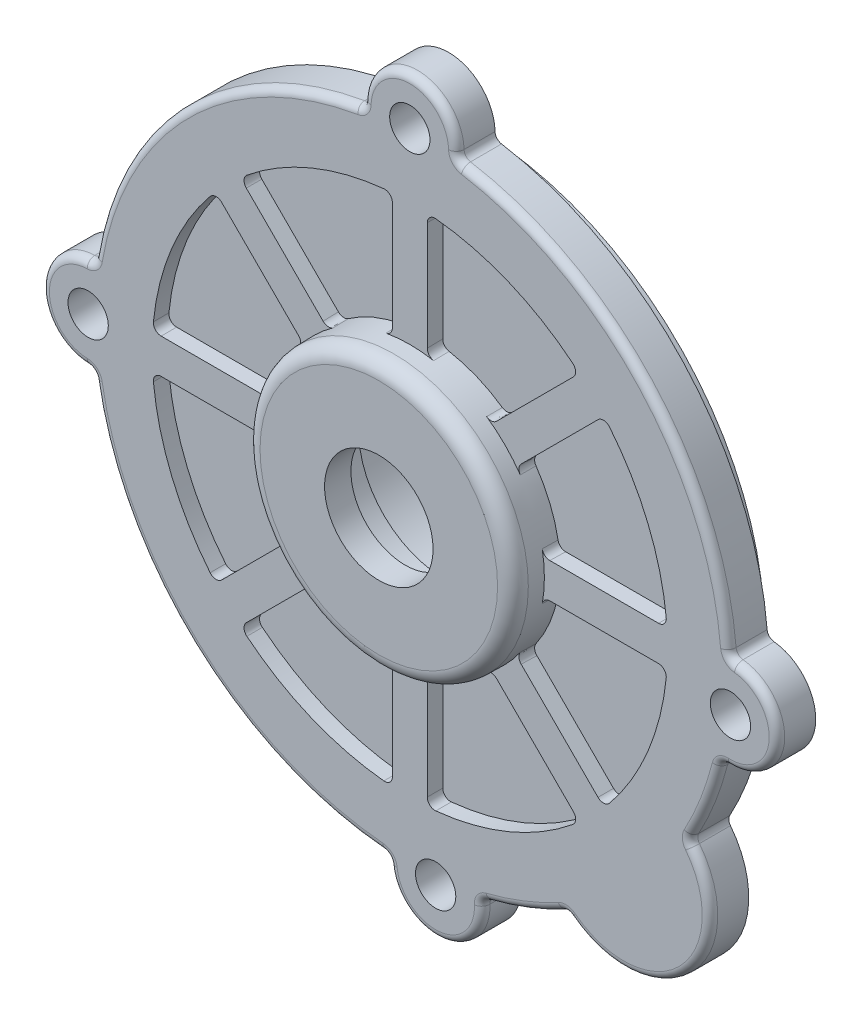
SolidWorks part; units mm, degrees
material "356.0-T6 Moulage permanent (SS)"
ref_plane "Plan de face" through (0, 0, 0) normal (0, 0, 1) x (1, 0, 0)
ref_plane "Plan de dessus" through (0, 0, 0) normal (0, 1, 0) x (1, 0, 0)
ref_plane "Plan de droite" through (0, 0, 0) normal (1, 0, 0) x (0, 0, -1)
ref_axis "Axe1" through (0, 0, 0) along (0, 0, 1)
sketch "Esquisse17" plane through (0, 0, 0) normal (0, 0, 1) x (1, 0, 0)
  line L0 (0, 0) -> (-27.5772, 27.5772) construction
  line L1 (65.7399, 0) -> (-65.7399, 0) construction
  line L2 (-27.5772, 69.0772) -> (-27.5772, 27.5772) construction
  line L3 (-69.0772, 27.5772) -> (-27.5772, 27.5772) construction
  line L4 (-30.7591, 30.7591) -> (30.7591, 30.7591) construction
  line L5 (30.7591, 30.7591) -> (30.7591, -30.7591) construction
  line L6 (-30.7591, 30.7591) -> (-30.7591, -30.7591) construction
  line L7 (30.7591, -30.7591) -> (-30.7591, -30.7591) construction
  line L8 (0, 0) -> (30.7591, 30.7591) construction
  circle A0 centre (0, 0) radius 50.45
  circle A1 centre (-27.5772, 27.5772) radius 41.25
  circle A2 centre (-27.5772, 27.5772) radius 41.5 construction
  circle A3 centre (0, 0) radius 43.5 construction
  point P8 (13.7889, 24.2458)
  point P9 (-24.2458, -13.7889)
  point P10 (-27.5772, 69.0772)
  point P11 (-69.0772, 27.5772)
  dimension "D1" = 100.9
  dimension "D2" = 82.5
  dimension "D8" = 58.6899
  dimension "D6" = 83
  dimension "D9" = 87
  dimension "D3" = 39
  dimension "D4" = 45
  dimension "D5" = 61
  dimension "D7" = 53.7893
ref_axis "Axe2" through (-27.5772, 27.5772, 0) along (0, 0, 1)
ref_plane "Plan1" through (-27.5772, 0, 0) normal (1, 0, 0) x (0, 0, -1)
sketch "Esquisse18" plane through (0, 0, 0) normal (0, 0, 1) x (1, 0, 0)
  arc A0 (2.9197, 7.0709) -> (-7.0709, -2.9197) centre (-27.5772, 27.5772) ccw
  arc A1 (8.3776, 7.3579) -> (-7.3579, -8.3776) centre (-27.5772, 27.5772) ccw
  arc A2 (-7.3579, -8.3776) -> (8.3776, 7.3579) centre (0, 0) ccw
  arc A3 (-7.0709, -2.9197) -> (2.9197, 7.0709) centre (0, 0) ccw
  dimension "D1" = 4.5
  dimension "D2" = 82.5
  dimension "D3" = 91.4
  dimension "D4" = 3.5
sketch "Esquisse27" plane through (0, 0, 0) normal (0, 0, 1) x (1, 0, 0)
  circle A0 centre (0, 0) radius 50.45 construction
  circle A1 centre (0, 0) radius 50.45
sketch "Esquisse28" plane through (0, 0, 0) normal (0, 0, 1) x (1, 0, 0)
  arc A0 (-21.5789, 69.2198) -> (-33.5755, 69.2198) centre (-27.5772, 69.0772) ccw
  arc A1 (13.4496, 18.2554) -> (14.4126, 30.2133) centre (13.7889, 24.2458) ccw
  arc A2 (-30.2133, -14.4126) -> (-18.2554, -13.4496) centre (-24.2458, -13.7889) ccw
  arc A3 (-69.2198, 33.5755) -> (-69.2198, 21.5789) centre (-69.0772, 27.5772) ccw
  circle A4 centre (-27.5772, 27.5772) radius 41.25 construction
  arc A5 (-34.4096, 68.2574) -> (-68.2574, 34.4096) centre (-27.5772, 27.5772) ccw
  arc A6 (13.5202, 31.122) -> (-20.7448, 68.2574) centre (-27.5772, 27.5772) ccw
  arc A7 (-68.2574, 20.7448) -> (-31.122, -13.5202) centre (-27.5772, 27.5772) ccw
  arc A8 (-17.5013, -12.4233) -> (-7.9466, -8.7023) centre (-27.5772, 27.5772) ccw
  arc A9 (13.5202, 31.122) -> (14.4126, 30.2133) centre (14.5165, 31.2079) ccw
  arc A10 (12.4233, 17.5013) -> (13.4496, 18.2554) centre (13.393, 17.257) cw
  arc A11 (-18.2554, -13.4496) -> (-17.5013, -12.4233) centre (-17.257, -13.393) cw
  arc A12 (-30.2133, -14.4126) -> (-31.122, -13.5202) centre (-31.2079, -14.5165) ccw
  arc A13 (-68.2574, 20.7448) -> (-69.2198, 21.5789) centre (-69.2436, 20.5791) ccw
  arc A14 (-69.2198, 33.5755) -> (-68.2574, 34.4096) centre (-69.2436, 34.5752) ccw
  arc A15 (-34.4096, 68.2574) -> (-33.5755, 69.2198) centre (-34.5752, 69.2436) ccw
  arc A16 (-21.5789, 69.2198) -> (-20.7448, 68.2574) centre (-20.5791, 69.2436) ccw
  arc A17 (-6.8558, -8.7932) -> (8.7932, 6.8558) centre (0, 0) ccw
  arc A18 (8.7023, 7.9466) -> (12.4233, 17.5013) centre (-27.5772, 27.5772) ccw
  arc A19 (-6.8558, -8.7932) -> (-7.9466, -8.7023) centre (-7.4707, -9.5818) ccw
  arc A20 (8.7023, 7.9466) -> (8.7932, 6.8558) centre (9.5818, 7.4707) ccw
  arc A21 (-7.3579, -8.3776) -> (8.3776, 7.3579) centre (0, 0) ccw construction
  point P24 (-18.3589, -12.6296)
  point P29 (-68.3942, 21.6162)
  point P43 (8.3776, 7.3579)
  dimension "D1" = 12
  dimension "D2" = 1
  dimension "D3" = 1
extrude "Boss.-Extru.1" add sketch "Esquisse28" along normal blind 5
sketch "Esquisse29" plane through (0, 0, 0) normal (0, 0, -1) x (-1, 0, 0)
  circle A0 centre (27.5772, 27.5772) radius 37.75
  circle A2 centre (27.5772, 27.5772) radius 41.25 construction
  dimension "D1" = 3.5
extrude "Boss.-Extru.2" add sketch "Esquisse29" along normal blind 3
sketch "Esquisse33" plane through (0, 0, 5) normal (0, 0, 1) x (1, 0, 0)
  circle A0 centre (-27.5772, 69.0772) radius 2.6
  circle A1 centre (13.7889, 24.2458) radius 2.6
  circle A2 centre (-24.2458, -13.7889) radius 2.6
  circle A3 centre (-69.0772, 27.5772) radius 2.6
  dimension "D1" = 5.2
extrude "Enlèv. mat.-Extru.1" cut sketch "Esquisse33" against normal through all
sketch "Esquisse34" plane through (0, 0, 5) normal (0, 0, 1) x (1, 0, 0)
  line L0 (-27.5772, 69.0772) -> (-27.5772, 27.5772) construction
  line L1 (-27.5772, 27.5772) -> (-51.3979, 85.0855) construction
  line L3 (-29.8272, 59.663) -> (-29.8272, 33.0091)
  line L4 (-48.6743, 51.8563) -> (-29.8272, 33.0091)
  arc A0 (-30.9279, 60.6579) -> (-48.5994, 53.3381) centre (-27.5772, 27.5772) ccw
  circle A1 centre (-27.5772, 27.5772) radius 41.25 construction
  arc A2 (-48.6743, 51.8563) -> (-48.5994, 53.3381) centre (-47.9672, 52.5634) cw
  arc A3 (-30.9279, 60.6579) -> (-29.8272, 59.663) centre (-30.8272, 59.663) cw
  dimension "D2" = 8
  dimension "D3" = 1
  dimension "D1" = 4.5
  dimension "D4" = 22.5
extrude "Enlèv. mat.-Extru.2" cut sketch "Esquisse34" against normal blind 2
pattern_circular "Répétition circulaire1" count 8 over 360 about axis through (-27.5772, 27.5772, 0) along (0, 0, 1) of "Enlèv. mat.-Extru.2"
sketch "Esquisse31" plane through (-27.5772, 0, 0) normal (1, 0, 0) x (0, 0, -1)
  line L0 (-22.6964, 27.5772) -> (15.8803, 27.5772) construction
  line L1 (0, 27.5772) -> (-61.3604, 27.5772) construction
  line L2 (3, 43.5772) -> (3, 45.0772)
  line L3 (3, 45.0772) -> (-7.0349, 44.902)
  line L4 (-9, 42.9023) -> (-9, 27.5772)
  line L5 (7.4, 27.5772) -> (-9, 27.5772)
  line L6 (-5, 68.2574) -> (-5, 31.122) construction
  line L7 (3, -10.1728) -> (3, 65.3272) construction
  line L8 (3, 43.5772) -> (6.4175, 43.5175)
  line L9 (7.4, 42.5177) -> (7.4, 27.5772)
  arc A0 (-9, 42.9023) -> (-7.0349, 44.902) centre (-7, 42.9023) cw
  arc A1 (6.4175, 43.5175) -> (7.4, 42.5177) centre (6.4, 42.5177) cw
  dimension "D3" = 2
  dimension "D8" = 1
  dimension "D1" = 35
  dimension "D2" = 1
  dimension "D4" = 4
  dimension "D5" = 4.4
  dimension "D6" = 32
  dimension "D7" = 1
revolve "Révolution1" add sketch "Esquisse31" angle 360 about L0
sketch "Esquisse32" plane through (-27.5772, 0, 0) normal (1, 0, 0) x (0, 0, -1)
  line L0 (-15.8258, 27.5772) -> (7.4146, 27.5772) construction
  line L1 (-0.6, 40.5772) -> (7.4, 40.5772)
  line L2 (-0.6, 40.5772) -> (-0.6, 38.5772)
  line L3 (-9, 27.5772) -> (7.4, 27.5772)
  line L4 (7.4, 40.5772) -> (7.4, 27.5772)
  line L5 (0, 27.5772) -> (-61.3604, 27.5772) construction
  line L7 (-5.6, 34.5772) -> (-9, 34.5772)
  line L8 (-9, 34.5772) -> (-9, 27.5772)
  line L9 (-9, 42.9023) -> (-9, 12.252) construction
  line L10 (7.4, 12.6367) -> (7.4, 42.5177) construction
  line L11 (-0.6, 38.5772) -> (-5.6, 38.5772)
  line L12 (-5.6, 38.5772) -> (-5.6, 34.5772)
  line L13 (0, 43.6295) -> (3, 43.5772)
  line L14 (3, 43.5772) -> (6.4175, 43.5175) construction
  line L15 (0, 43.6295) -> (0, 62.5772)
  line L16 (0, 62.5772) -> (3, 62.5772)
  line L17 (3, 62.5772) -> (3, 43.5772)
  line L18 (3, -10.1728) -> (3, 65.3272) construction
  dimension "D1" = 26
  dimension "D2" = 8
  dimension "D3" = 14
  dimension "D4" = 22
  dimension "D5" = 5
  dimension "D6" = 3
  dimension "D7" = 70
revolve "Enlèvement de matière-Révolution1" cut sketch "Esquisse32" angle 360 about L0
fillet "Congé1" radius 1 20 edges at (-33.8195, 68.5887, 5) (-27.5772, 75.0772, 5) (-21.3348, 68.5887, 5) (2.7391, 55.5501, 5) (13.8031, 30.5072, 5) (19.7695, 23.7642, 5) (12.8009, 18.0629, 5) (-12.6079, -10.8609, 5) (-18.0629, -12.8009, 5) (-23.7642, -19.7695, 5) (-30.5072, -13.8031, 5) (-55.5501, -2.7391, 5) (-68.5887, 21.3348, 5) (-75.0772, 27.5772, 5) (-68.5887, 33.8195, 5) (-56.7453, 56.7453, 5) (10.8609, 12.6079, 5) (8.5853, 7.3876, 5) (7.8842, -7.8842, 5) (-7.3876, -8.5853, 5)
fillet "Congé2" radius 1 16 edges
fillet "Congé3" radius 1 2 edges at (7.4228, 27.5772, 0) (-11.5248, 27.5772, 0)
